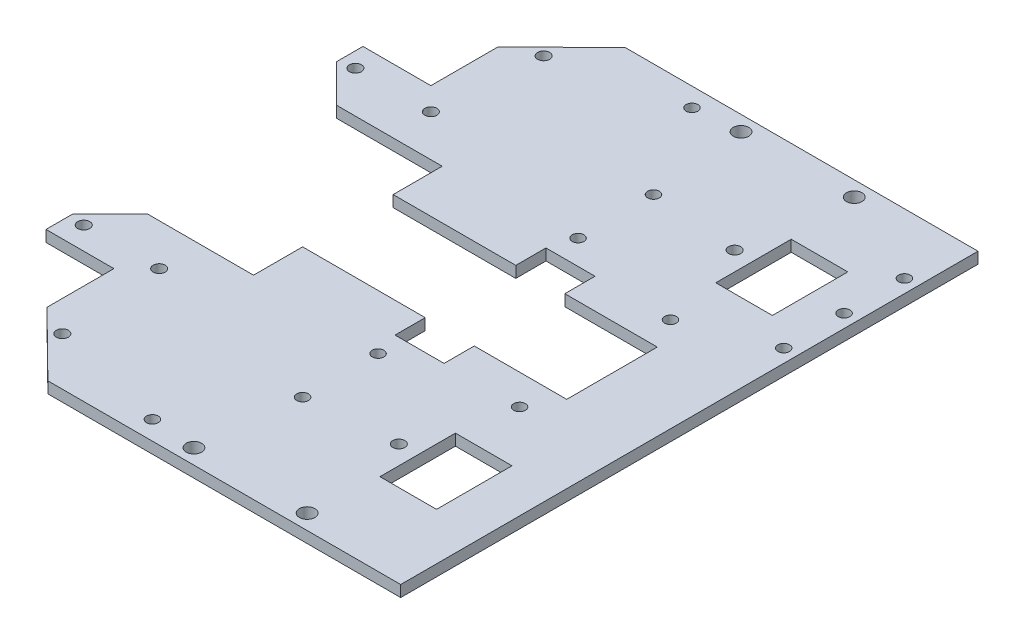
SolidWorks part; units mm, degrees
material "6061 合金"
ref_plane "前视基准面" through (0, 0, 0) normal (0, 0, 1) x (1, 0, 0)
ref_plane "上视基准面" through (0, 0, 0) normal (0, 1, 0) x (1, 0, 0)
ref_plane "右视基准面" through (0, 0, 0) normal (1, 0, 0) x (0, 0, -1)
sketch "草图1" plane through (0, 0, 0) normal (0, 1, 0) x (1, 0, 0)
  line L1 (-100, 76.5) -> (100, 76.5)
  line L2 (-100, 76.5) -> (-100, -76.5)
  line L3 (-100, -76.5) -> (100, -76.5)
  line L4 (100, 76.5) -> (100, -76.5)
  line L5 (-100, 76.5) -> (100, -76.5) construction
  line L6 (-100, -76.5) -> (100, 76.5) construction
  line L7 (-35.5, 20) -> (35.5, 20)
  line L8 (-35.5, 20) -> (-35.5, -20)
  line L9 (-35.5, -20) -> (35.5, -20)
  line L10 (35.5, 20) -> (35.5, -20)
  line L11 (-35.5, 20) -> (35.5, -20) construction
  line L12 (-35.5, -20) -> (35.5, 20) construction
  line L13 (-35.5, 20) -> (-100, 20)
  line L14 (-35.5, 20) -> (-35.5, -20)
  line L15 (-35.5, -20) -> (-100, -20)
  line L16 (-100, 20) -> (-100, -20)
  point P0 (0, 0)
  point P5 (0, 0)
  dimension "D1" = 153
  dimension "D2" = 200
  dimension "D3" = 71
  dimension "D4" = 40
extrude "凸台-拉伸1" add sketch "草图1" along normal blind 3 contours L9 L15 L2 L3 L4 L1 L13 L7 L10 region at (0, 0, -73.9819)
sketch "草图4" plane through (100, 0, 0) normal (1, 0, 0) x (0, 0, -1)
  line L1 (-76.5, 3) -> (76.5, 3)
  line L2 (-76.5, 3) -> (-76.5, 0)
  line L3 (-76.5, 0) -> (76.5, 0)
  line L4 (76.5, 3) -> (76.5, 0)
extrude "凸台-拉伸2" add sketch "草图4" along normal blind 50
sketch "草图5" plane through (0, 0, 0) normal (0, -1, 0) x (1, 0, 0)
  circle A0 centre (102, 30.5) radius 43.5
extrude "切除-拉伸2" cut sketch "草图5" against normal blind 10
sketch "草图6" plane through (-100, 0, 0) normal (-1, 0, 0) x (0, 0, 1)
  line L0 (-76.5, 3) -> (-20, 3) construction
  line L1 (-30, 3) -> (-20, 3)
  line L2 (-30, 3) -> (-30, 0)
  line L3 (-30, 0) -> (-20, 0)
  line L4 (-20, 3) -> (-20, 0)
  line L5 (-20, 0) -> (20, 0) construction
  line L6 (20, 0) -> (30, 0)
  line L7 (20, 0) -> (20, 3)
  line L8 (20, 3) -> (30, 3)
  line L9 (30, 0) -> (30, 3)
  line L10 (20, 3) -> (76.5, 3) construction
  dimension "D1" = 10
  dimension "D2" = 10
extrude "切除-拉伸3" cut sketch "草图6" against normal blind 70
sketch "草图7" plane through (0, 3, 0) normal (0, 1, 0) x (1, 0, 0)
  circle A0 centre (102, -30.5) radius 43.5
  circle A1 centre (102, -30.5) radius 39.5
  dimension "D1" = 79
extrude "凸台-拉伸3" add sketch "草图7" against normal up to surface (3 mm away) up to face at (102, 0, -13)
sketch "草图8" plane through (0, 3, 0) normal (0, 1, 0) x (1, 0, 0)
  line L1 (35.5, 20) -> (15.5, 20)
  line L2 (35.5, 20) -> (35.5, 12)
  line L3 (35.5, 12) -> (15.5, 12)
  line L4 (15.5, 20) -> (15.5, 12)
  line L5 (35.5, -20) -> (15.5, -20)
  line L6 (35.5, -20) -> (35.5, -12)
  line L7 (35.5, -12) -> (15.5, -12)
  line L8 (15.5, -20) -> (15.5, -12)
  dimension "D1" = 20
  dimension "D2" = 20
  dimension "D3" = 8
  dimension "D4" = 8
extrude "凸台-拉伸4" add sketch "草图8" against normal up to surface (3 mm away) up to face at (-12.4167, 0, 0)
sketch "草图9" plane through (0, 3, 0) normal (0, 1, 0) x (1, 0, 0)
  line L0 (-30, -20) -> (15.5, -20) construction
  line L1 (2.5, -20) -> (-15.5, -20)
  line L2 (2.5, -20) -> (2.5, -12)
  line L3 (2.5, -12) -> (-15.5, -12)
  line L4 (-15.5, -20) -> (-15.5, -12)
  line L5 (15.5, -12) -> (15.5, -20) construction
  line L6 (15.5, 20) -> (-30, 20) construction
  line L7 (2.5, 20) -> (-15.5, 20)
  line L8 (2.5, 20) -> (2.5, 12)
  line L9 (2.5, 12) -> (-15.5, 12)
  line L10 (-15.5, 20) -> (-15.5, 12)
  dimension "D1" = 13
  dimension "D2" = 18
  dimension "D3" = 8
  dimension "D4" = 8
  dimension "D5" = 18
extrude "凸台-拉伸5" add sketch "草图9" against normal up to surface (3 mm away) up to face at (-5.4375, 0, 0)
sketch "草图11" plane through (-100, 0, 0) normal (-1, 0, 0) x (0, 0, 1)
  line L0 (-76.5, 0) -> (-30, 0) construction
  line L1 (-30, 3) -> (-76.5, 3)
  line L2 (-30, 3) -> (-30, 0)
  line L3 (-30, 0) -> (-76.5, 0)
  line L4 (-76.5, 3) -> (-76.5, 0)
extrude "切除-拉伸4" cut sketch "草图11" against normal blind 50
sketch "草图38" plane through (-100, 0, 0) normal (-1, 0, 0) x (0, 0, 1)
  line L0 (30, 0) -> (30, 3)
  line L1 (30, 3) -> (76.5, 3)
  line L2 (76.5, 3) -> (76.5, 0)
  line L3 (76.5, 0) -> (30, 0)
extrude "切除-拉伸29" cut sketch "草图38" against normal up to surface (50 mm away) up to face at (-50, 1.5, -53.25)
sketch "草图15" plane through (0, 0, 0) normal (0, -1, 0) x (-1, 0, 0)
  line L0 (-144, 70.5) -> (-144, 18.5)
  line L1 (-150, 76.5) -> (-61, 76.5)
  line L2 (-150, 76.5) -> (-150, 12.5)
  line L3 (-150, 12.5) -> (-61, 12.5)
  line L4 (-61, 76.5) -> (-61, 12.5)
  line L5 (-144, 18.5) -> (-67, 18.5)
  line L6 (-67, 70.5) -> (-67, 18.5)
  line L7 (-144, 70.5) -> (-67, 70.5)
  dimension "D1" = 6
extrude "切除-拉伸7" cut sketch "草图15" against normal blind 10 contours L0 L5 L6 L7
sketch "草图16" plane through (67, 0, 0) normal (1, 0, 0) x (0, 0, -1)
  line L1 (18.5, 3) -> (70.5, 3)
  line L2 (18.5, 3) -> (18.5, 0)
  line L3 (18.5, 0) -> (70.5, 0)
  line L4 (70.5, 3) -> (70.5, 0)
extrude "切除-拉伸8" cut sketch "草图16" against normal blind 3.1
sketch "草图17" plane through (0, 0, -70.5) normal (0, 0, 1) x (1, 0, 0)
  line L1 (63.9, 3) -> (144, 3)
  line L2 (63.9, 3) -> (63.9, 0)
  line L3 (63.9, 0) -> (144, 0)
  line L4 (144, 3) -> (144, 0)
extrude "切除-拉伸9" cut sketch "草图17" against normal up to next
sketch "草图18" plane through (0, 3, 0) normal (0, 1, 0) x (1, 0, 0)
  line L1 (144, 18.5) -> (150, 18.5)
  line L2 (144, 18.5) -> (144, 76.5)
  line L3 (144, 76.5) -> (150, 76.5)
  line L4 (150, 18.5) -> (150, 76.5)
extrude "切除-拉伸10" cut sketch "草图18" against normal blind 10
sketch "草图19" plane through (150, 0, 0) normal (1, 0, 0) x (0, 0, -1)
  line L1 (-76.5, 3) -> (18.5, 3)
  line L2 (-76.5, 3) -> (-76.5, 0)
  line L3 (-76.5, 0) -> (18.5, 0)
  line L4 (18.5, 3) -> (18.5, 0)
extrude "切除-拉伸11" cut sketch "草图19" against normal blind 5.5
sketch "草图20" plane through (0, 0, -18.5) normal (0, 0, -1) x (-1, 0, 0)
  line L1 (-144.5, 3) -> (-63.9, 3)
  line L2 (-144.5, 3) -> (-144.5, 0)
  line L3 (-144.5, 0) -> (-63.9, 0)
  line L4 (-63.9, 3) -> (-63.9, 0)
extrude "切除-拉伸12" cut sketch "草图20" against normal blind 6
sketch "草图21" plane through (63.9, 0, 0) normal (1, 0, 0) x (0, 0, -1)
  line L0 (12.5, 0) -> (76.5, 0) construction
  line L1 (12.5, 3) -> (76.5, 3)
  line L2 (12.5, 3) -> (12.5, 0)
  line L3 (12.5, 0) -> (76.5, 0)
  line L4 (76.5, 3) -> (76.5, 0)
extrude "切除-拉伸13" cut sketch "草图21" against normal blind 3.4
sketch "草图22" plane through (0, 0, 0) normal (0, -1, 0) x (-1, 0, 0)
  circle A0 centre (44, 36) radius 1.5
extrude "切除-拉伸14" cut sketch "草图22" against normal up to next
mirror "镜向2" about plane through (0, 0, 0) normal (0, 0, 1) of "切除-拉伸14"
sketch "草图24" plane through (0, 0, 0) normal (0, -1, 0) x (-1, 0, 0)
  circle A0 centre (-139.5, -71.5) radius 1.5
extrude "切除-拉伸15" cut sketch "草图24" against normal blind 14
sketch "草图25" plane through (0, 0, 0) normal (0, -1, 0) x (1, 0, 0)
  circle A0 centre (78.0814, 70.3762) radius 1.55
extrude "切除-拉伸16" cut sketch "草图25" against normal blind 14
pattern_circular "阵列(圆周)1" count 3 every 90 about axis through (102, 3, 30.5) along (0, 1, 0) of "切除-拉伸16"
sketch "草图26" plane through (0, 3, 0) normal (0, 1, 0) x (1, 0, 0)
  circle A0 centre (68.8964, -69.9513) radius 1.55
  circle A1 centre (62.5487, -63.6036) radius 1.55
  dimension "D1" = 3.1
extrude "切除-拉伸17" cut sketch "草图26" against normal blind 14
pattern_circular "阵列(圆周)2" count 3 every 90 about axis through (102, 3, 30.5) along (0, 1, 0) of "切除-拉伸17"
sketch "草图27" plane through (0, 3, 0) normal (0, 1, 0) x (1, 0, 0)
  line L0 (60.5, 76.5) -> (53.5, 76.5)
  line L1 (-50, 76.5) -> (60.5, 76.5) construction
  line L2 (60.5, 12.5) -> (53.5, 76.5) construction
  line L3 (57, 76.5) -> (57, 44.5) construction
  line L4 (57, 44.5) -> (57, 12.5) construction
  circle A0 centre (57, 28.5) radius 1.55
  circle A1 centre (57, 44.5) radius 1.55
  circle A2 centre (57, 60.5) radius 1.55
  dimension "D2" = 3.1
  dimension "D3" = 3.1
  dimension "D4" = 3.1
  dimension "D1" = 7
extrude "切除-拉伸18" cut sketch "草图27" against normal blind 10 contours A2 | A1 | A0 region at (57, 3, -28.5) region at (57, 3, -44.5) region at (57, 3, -60.5)
sketch "草图30" plane through (0, 3, 0) normal (0, 1, 0) x (1, 0, 0)
  line L0 (60.5, 44.5) -> (40.5, 44.5) construction
  line L1 (60.5, 76.5) -> (60.5, 12.5) construction
  line L3 (33, 54.5) -> (48, 54.5)
  line L4 (33, 54.5) -> (33, 34.5)
  line L5 (33, 34.5) -> (48, 34.5)
  line L6 (48, 54.5) -> (48, 34.5)
  line L7 (33, 54.5) -> (48, 34.5) construction
  line L8 (33, 34.5) -> (48, 54.5) construction
  dimension "D1" = 20
  dimension "D2" = 15
  dimension "D3" = 20
extrude "切除-拉伸21" cut sketch "草图30" against normal blind 10
mirror "镜向5" about plane through (0, 0, 0) normal (0, 0, 1) of "切除-拉伸21"
sketch "草图31" plane through (0, 3, 0) normal (0, 1, 0) x (1, 0, 0)
  line L0 (35.5, 0) -> (35.5, 20)
  line L1 (35.5, 12) -> (35.5, -12) construction
  circle A0 centre (35.5, 20) radius 1.55
  dimension "D2" = 3.1
  dimension "D1" = 20
extrude "切除-拉伸22" cut sketch "草图31" against normal blind 10 contours A0
mirror "镜向6" about plane through (0, 0, 0) normal (0, 0, 1) of "切除-拉伸22"
sketch "Sketch1" plane through (0, 3, 0) normal (0, 1, 0) x (1, 0, 0)
  line L1 (-50, 30) -> (-68, 30)
  line L2 (-50, 30) -> (-50, 42)
  line L3 (-50, 42) -> (-68, 42)
  line L4 (-68, 30) -> (-68, 42)
  dimension "D1" = 12
extrude "Boss-Extrude1" add sketch "Sketch1" against normal up to surface (3 mm away) up to face at (35.5, 0, 21.55)
mirror "Mirror1" about plane through (0, 0, 0) normal (0, 0, 1) of "Boss-Extrude1"
sketch "Sketch2" plane through (0, 3, 0) normal (0, 1, 0) x (1, 0, 0)
  circle A0 centre (-64, 36) radius 1.6
  circle A2 centre (-44, 36) radius 1.5 construction
  circle A3 centre (-44, 36) radius 1.6
  dimension "D1" = 3.2
  dimension "D2" = 20
  dimension "D3" = 0
  dimension "D4" = 3.2
extrude "Cut-Extrude1" cut sketch "Sketch2" against normal blind 10
mirror "Mirror2" about plane through (0, 0, 0) normal (0, 0, 1) of "Cut-Extrude1"
sketch "Sketch4" plane through (0, 3, 0) normal (0, 1, 0) x (1, 0, 0)
  line L0 (-30, 20) -> (-30, 30) construction
  line L1 (-30, -30) -> (-68, -30)
  line L2 (-30, -30) -> (-30, -25)
  line L3 (-30, -25) -> (-68, -25)
  line L4 (-68, -30) -> (-68, -25)
  line L5 (-68, 30) -> (-30, 30)
  line L6 (-68, 30) -> (-68, 25)
  line L7 (-68, 25) -> (-30, 25)
  line L8 (-30, 30) -> (-30, 25)
  line L10 (-15.5, 12) -> (-30, 12)
  line L11 (-15.5, 12) -> (-15.5, 20)
  line L12 (-15.5, 20) -> (-30, 20)
  line L13 (-30, 12) -> (-30, 20)
  line L14 (-15.5, -12) -> (-30, -12)
  line L15 (-15.5, -12) -> (-15.5, -20)
  line L16 (-15.5, -20) -> (-30, -20)
  line L17 (-30, -12) -> (-30, -20)
  dimension "D1" = 5
  dimension "D2" = 5
extrude "Boss-Extrude3" add sketch "Sketch4" against normal up to surface (3 mm away) up to face at (-64, 0, 37.6)
sketch "草图32" plane through (0, 0, 0) normal (0, -1, 0) x (-1, 0, 0)
  circle A0 centre (-1.7, 72.5) radius 1.65
  circle A1 centre (-26.7, 72.5) radius 1.65
extrude "切除-拉伸23" cut sketch "草图32" against normal blind 6
mirror "镜向7" about plane through (0, 0, 0) normal (0, 0, 1) of "切除-拉伸23"
sketch "草图33" plane through (0, 3, 0) normal (0, 1, 0) x (1, 0, 0)
  circle A0 centre (4.5, 46.5) radius 1.55
extrude "切除-拉伸24" cut sketch "草图33" against normal up to next
sketch "草图34" plane through (0, 3, 0) normal (0, 1, 0) x (1, 0, 0)
  circle A0 centre (4.5, 26.5) radius 1.55
extrude "切除-拉伸25" cut sketch "草图34" against normal up to next and the other way through all
mirror "镜向8" about plane through (0, 0, 0) normal (0, 0, 1) of "切除-拉伸25", "切除-拉伸24"
sketch "草图36" plane through (0, 3, 0) normal (0, 1, 0) x (1, 0, 0)
  circle A0 centre (-41.8955, 63.7727) radius 1.6
  circle A1 centre (-56.0386, 49.6316) radius 1.6
  dimension "D1" = 3.2
  dimension "D2" = 3.2
extrude "切除-拉伸27" cut sketch "草图36" against normal blind 10
mirror "镜向10" about plane through (0, 0, 0) normal (0, 0, 1) of "切除-拉伸27"
sketch "Sketch5" plane through (0, 3, 0) normal (0, 1, 0) x (1, 0, 0)
  circle A0 centre (1.7, 72.5) radius 2.05
  circle A1 centre (26.7, 72.5) radius 2.05
  circle A2 centre (1.7, -72.5) radius 2.05
  circle A3 centre (26.7, -72.5) radius 2.05
  dimension "D1" = 4.1
  dimension "D2" = 4.1
  dimension "D3" = 4.1
  dimension "D4" = 4.1
extrude "Cut-Extrude2" cut sketch "Sketch5" against normal blind 10
sketch "Sketch6" plane through (0, 3, 0) normal (0, 1, 0) x (1, 0, 0)
  line L0 (33, 54.5) -> (33, 34.5) construction
  line L1 (33, -54.5) -> (33, -34.5) construction
  circle A0 centre (28, 44.5) radius 1.6
  circle A1 centre (28, -44.5) radius 1.6
  point P4 (33, 44.5)
  point P9 (33, -44.5)
  dimension "D1" = 3.2
  dimension "D2" = 5
  dimension "D3" = 3.2
  dimension "D4" = 5
extrude "Cut-Extrude3" cut sketch "Sketch6" against normal blind 10
sketch "草图37" plane through (35.5, 0, 0) normal (-1, 0, 0) x (0, 0, 1)
  line L1 (-12, 3) -> (12, 3)
  line L2 (-12, 3) -> (-12, 0)
  line L3 (-12, 0) -> (12, 0)
  line L4 (12, 3) -> (12, 0)
extrude "切除-拉伸28" cut sketch "草图37" against normal blind 4.5
chamfer "Chamfer1" distance 10 angle 45 2 edges at (-68, 1.5, -25) (-68, 1.5, 25)
sketch "Sketch8" plane through (0, 3, 0) normal (0, 1, 0) x (1, 0, 0)
  circle A0 centre (-10.3, -71.5) radius 1.55
extrude "Cut-Extrude5" cut sketch "Sketch8" against normal blind 10
mirror "Mirror3" about plane through (0, 0, 0) normal (0, 0, 1) of "Cut-Extrude5"
sketch "草图39" plane through (0, 3, 0) normal (0, 1, 0) x (1, 0, 0)
  line L0 (-68, 42) -> (-68, 85.4837)
  line L1 (-50, 76.5) -> (-68, 76.5)
  line L2 (-68, 76.5) -> (-33, 76.5)
  line L3 (-50, 76.5) -> (60.5, 76.5) construction
  line L4 (-33, 76.5) -> (-68, 42)
  dimension "D1" = 35
extrude "切除-拉伸30" cut sketch "草图39" against normal blind 10 contours L4 L2 L1 L0 region at (-56.3333, 3, -65)
mirror "镜向11" about plane through (0, 0, 0) normal (0, 0, 1) of "切除-拉伸30"
sketch "草图40" plane through (0, 3, 0) normal (0, 1, 0) x (1, 0, 0)
  line L0 (1.7, -72.5) -> (31.7, -72.5)
  line L1 (1.7, 72.5) -> (31.7, 72.5)
  circle A0 centre (26.7, -72.5) radius 2.05
  circle A1 centre (31.7, -72.5) radius 2.05
  circle A2 centre (26.7, 72.5) radius 2.05
  circle A3 centre (31.7, 72.5) radius 2.05
  dimension "D1" = 30
extrude "凸台-拉伸6" add sketch "草图40" against normal blind 3 contours L1 A2 | L1 A2 | L0 A0 | L0 A0 region at (26.7, 3, 71.63) region at (26.7, 3, 73.37) region at (26.7, 3, -73.37) region at (26.7, 3, -71.63)
extrude "切除-拉伸31" cut sketch "草图40<3>" against normal blind 10 contours A1 | A3 region at (31.7, 3, 70.508) region at (31.7, 3, -74.492)
sketch "草图40<3>" plane through (0, 3, 0) normal (0, 1, 0) x (1, 0, 0) same geometry as "草图40"
sketch "草图41" plane through (0, 3, 0) normal (0, 1, 0) x (1, 0, 0)
  line L0 (60.5, 12.5) -> (60.5, -76.5)
  line L1 (-33, -76.5) -> (144.5, -76.5) construction
  line L2 (60.5, -76.5) -> (144.5, -76.5)
  line L3 (144.5, -76.5) -> (144.5, 12.5)
  line L4 (144.5, 12.5) -> (60.5, 12.5)
extrude "切除-拉伸32" cut sketch "草图41" against normal blind 10
